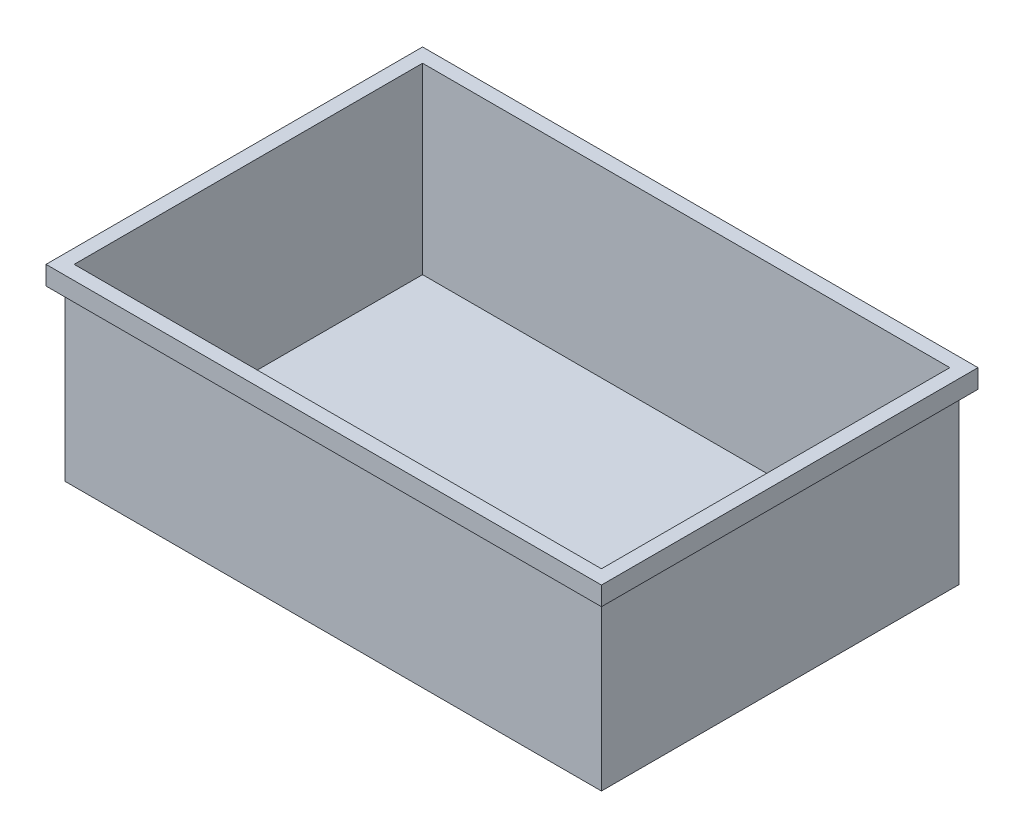
SolidWorks part; units mm, degrees
ref_plane "Front Plane" through (0, 0, 0) normal (0, 0, 1) x (1, 0, 0)
ref_plane "Top Plane" through (0, 0, 0) normal (0, 1, 0) x (1, 0, 0)
ref_plane "Right Plane" through (0, 0, 0) normal (1, 0, 0) x (0, 0, -1)
sketch "Sketch1" plane through (0, 0, 0) normal (0, 1, 0) x (1, 0, 0)
  line L5 (0, 0) -> (228.6, 0)
  line L6 (0, 0) -> (0, 152.4)
  line L7 (0, 152.4) -> (228.6, 152.4)
  line L8 (228.6, 0) -> (228.6, 152.4)
  dimension "D1" = 152.4
  dimension "D2" = 228.6
extrude "Boss-Extrude1" add sketch "Sketch1" along normal blind 80
shell "Shell1" thickness 2 removed face at (114.3, 80, -76.2)
sketch "Sketch2" plane through (0, 80, 0) normal (0, 1, 0) x (1, 0, 0)
  line L6 (2, 2) -> (226.6, 2) construction
  line L11 (226.6, 2) -> (226.6, 150.4) construction
  line L12 (226.6, 150.4) -> (2, 150.4) construction
  line L13 (2, 150.4) -> (2, 2) construction
  line L14 (232.6, -4) -> (232.6, 156.4)
  line L15 (-4, -4) -> (232.6, -4)
  line L16 (-4, 156.4) -> (-4, -4)
  line L17 (232.6, 156.4) -> (-4, 156.4)
  line L18 (232.6, -4) -> (232.6, 156.4)
  line L19 (-4, -4) -> (232.6, -4)
  line L20 (-4, 156.4) -> (-4, -4)
  line L21 (232.6, 156.4) -> (-4, 156.4)
  line L22 (2, 2) -> (226.6, 2)
  line L23 (226.6, 2) -> (226.6, 150.4)
  line L24 (226.6, 150.4) -> (2, 150.4)
  line L25 (2, 150.4) -> (2, 2)
  dimension "D1" = 4
extrude "Boss-Extrude2" add sketch "Sketch2" against normal blind 10
chamfer "Chamfer1" distance 2 angle 45 8 edges at (228.6, 70, -76.2) (114.3, 70, 0) (0, 70, -76.2) (114.3, 70, -152.4) (232.6, 70, -76.2) (114.3, 70, -156.4) (-4, 70, -76.2) (114.3, 70, 4)
ref_plane "Plane1" through (0, 40, 0) normal (0, 1, 0) x (1, 0, 0)
